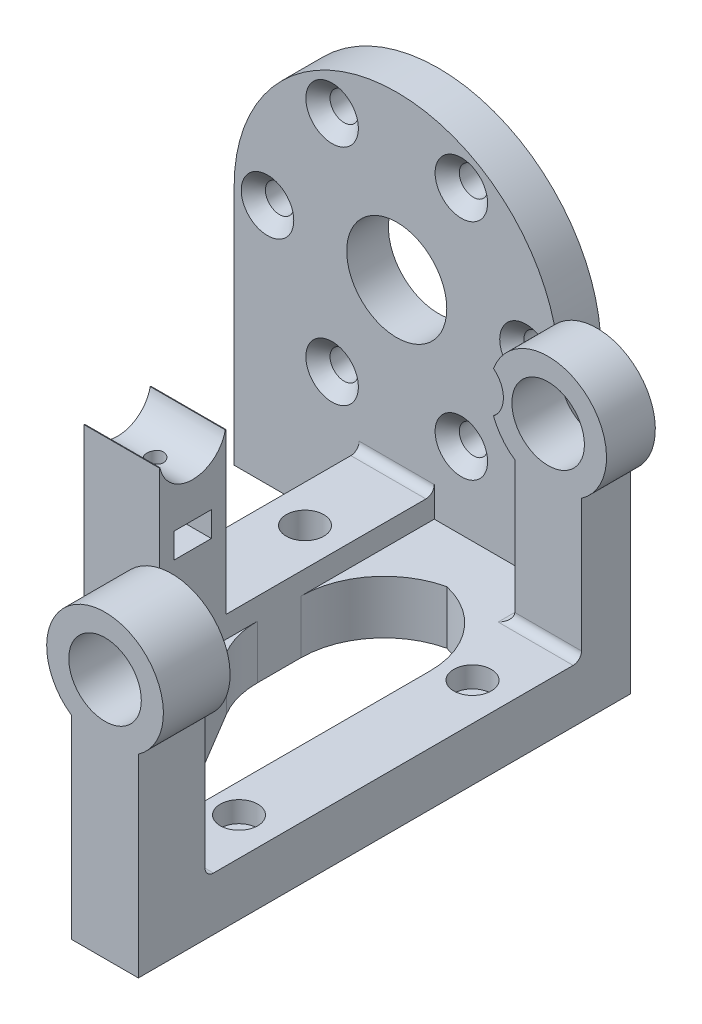
SolidWorks part; units mm, degrees
ref_plane "Front Plane" through (0, 0, 0) normal (0, 0, 1) x (1, 0, 0)
ref_plane "Top Plane" through (0, 0, 0) normal (0, 1, 0) x (1, 0, 0)
ref_plane "Right Plane" through (0, 0, 0) normal (1, 0, 0) x (0, 0, -1)
sketch "Sketch5" plane through (0, 0, 0) normal (0, 0, 1) x (1, 0, 0)
  line L0 (0, 0) -> (0, 15.5) construction
  circle A0 centre (0, 0) radius 19.5
  circle A1 centre (-7.75, 13.4234) radius 1.5
  circle A2 centre (0, 0) radius 6
  circle A3 centre (7.75, 13.4234) radius 1.5
  circle A4 centre (15.5, 0) radius 1.5
  circle A5 centre (7.75, -13.4234) radius 1.5
  circle A6 centre (-7.75, -13.4234) radius 1.5
  circle A7 centre (-15.5, 0) radius 1.5
  point P18 (0, 0)
  dimension "D2" = 3
  dimension "D3" = 39
  dimension "D4" = 12
  dimension "D1" = 15.5
  dimension "D5" = 6
extrude "Boss-Extrude1" add sketch "Sketch5" along normal blind 5
hole_wizard "CSK for M3 Flat Head Machine Screw1" positions "Sketch7" profile "Sketch6" countersink size "M3" standard "ANSI Metric" end condition through all
sketch "Sketch7" plane through (0, 0, 5) normal (0, 0, 1) x (1, 0, 0)
  point P0 (-15.5, 0)
  point P3 (-7.75, 13.4234)
  point P6 (7.75, 13.4234)
  point P9 (15.5, 0)
  point P12 (7.75, -13.4234)
  point P15 (-7.75, -13.4234)
sketch "Sketch6" plane through (-15.5, 0, 5) normal (1, 0, 0) x (0, -1, 0)
  line L0 (0, 0) -> (0, 5)
  line L1 (0, 5) -> (1.7, 5)
  line L2 (1.7, 5) -> (1.7, 1.45)
  line L3 (1.7, 1.45) -> (3.15, 0)
  line L5 (3.15, 0) -> (0, 0)
  line L6 (-1.7, 1.45) -> (-3.15, 0) construction
  line L11 (0, -6.35) -> (0, 107.95) construction
  dimension "Thru Hole Dia." = 3.4
  dimension "Thru Hole Depth" = 5
  dimension "Near C'Sink Dia." = 6.3
  dimension "Near C'Sink Angle" = 90
sketch "Sketch8" plane through (0, 0, 5) normal (0, 0, 1) x (1, 0, 0)
  line L0 (-19.5, 0) -> (-19.5, -25)
  line L1 (-19.5, -25) -> (19.5, -25)
  line L2 (19.5, -25) -> (19.5, 0)
  circle A0 centre (0, 0) radius 19.5 construction
  arc A1 (-19.5, 0) -> (19.5, 0) centre (0, 0) ccw
  dimension "D1" = 25
extrude "Boss-Extrude2" add sketch "Sketch8" against normal up to surface (5 mm away) up to face at (-13.8, 0, 0)
sketch "Sketch9" plane through (0, 0, 5) normal (0, 0, 1) x (1, 0, 0)
  line L0 (-19.5, -25) -> (19.5, -25) construction
  line L4 (-4.5, -20) -> (-4.5, -25)
  line L5 (4.5, -20) -> (-4.5, -25) construction
  line L6 (4.5, -25) -> (-4.5, -20) construction
  line L7 (-19.5, -25) -> (0, -22.5) construction
  line L8 (0, -22.5) -> (19.5, -25) construction
  line L9 (-4.5, -25) -> (4.5, -25)
  line L10 (-4.5, -20) -> (4.5, -20)
  line L11 (4.5, -20) -> (4.5, -25)
  point P0 (0, -22.5)
  dimension "D1" = 5
  dimension "D2" = 9
extrude "Boss-Extrude3" add sketch "Sketch9" along normal blind 32.9817
sketch "Sketch10" plane through (0.3712, -20, 0) normal (0, 1, 0) x (1, 0, 0)
  line L1 (-4.8712, -37.9817) -> (4.1288, -37.9817)
  line L2 (-4.8712, -37.9817) -> (-4.8712, -29.9817)
  line L3 (-4.8712, -29.9817) -> (4.1288, -29.9817)
  line L4 (4.1288, -37.9817) -> (4.1288, -29.9817)
  line L6 (-4.8712, -37.9817) -> (-4.8712, -5) construction
  line L7 (4.1288, -37.9817) -> (4.1288, -5) construction
  dimension "D1" = 8
extrude "Boss-Extrude4" add sketch "Sketch10" along normal blind 24
sketch "Sketch11" plane through (-4.5, 0, 0) normal (-1, 0, 0) x (0, 0, 1)
  line L0 (29.9817, 4) -> (29.9817, -20) construction
  line L2 (29.9817, 4) -> (37.9817, 4) construction
  line L3 (37.9817, 4) -> (37.9817, -25) construction
  line L4 (29.9817, 0) -> (27.1369, 2.0822)
  line L5 (27.1369, 2.0822) -> (27.3574, 4.8482)
  line L6 (27.3574, 4.8482) -> (32.7492, 5.4696)
  line L7 (32.7492, 5.4696) -> (41.4483, 5.0286)
  line L8 (41.4483, 5.0286) -> (40.8237, 2.383)
  line L9 (40.8237, 2.383) -> (37.9817, 0)
  line L10 (29.9817, -0.8) -> (30.0625, -0.8)
  line L11 (37.9009, -0.8) -> (37.9817, -0.8)
  line L12 (37.9817, 0) -> (37.9817, -0.8)
  line L13 (29.9817, -0.8) -> (29.9817, 0)
  arc A0 (30.0625, -0.8) -> (37.9009, -0.8) centre (33.9817, 0) ccw
  dimension "D1" = 0.8
extrude "Cut-Extrude1" cut sketch "Sketch11" against normal blind 20
sketch "Sketch12" plane through (0, -0.8, 0) normal (0, 1, 0) x (1, 0, 0)
  line L0 (-4.5, -29.9817) -> (4.5, -37.9817) construction
  line L1 (4.5, -29.9817) -> (-4.5, -37.9817) construction
  line L2 (4.5, -37.9009) -> (4.5, -30.0625) construction
  line L3 (4.5, -29.9817) -> (4.5, -5) construction
  circle A0 centre (0, -33.9817) radius 1
  dimension "D1" = 2
extrude "Cut-Extrude2" cut sketch "Sketch12" against normal blind 16
sketch "Sketch13" plane through (-4.5, 0, 0) normal (-1, 0, 0) x (0, 0, 1)
  line L0 (29.9817, -8.9707) -> (31.7317, -8.9707) construction
  line L1 (31.7317, -8.2443) -> (36.2317, -8.2443)
  line L2 (31.7317, -8.2443) -> (31.7317, -11.2443)
  line L3 (31.7317, -11.2443) -> (36.2317, -11.2443)
  line L4 (36.2317, -8.2443) -> (36.2317, -11.2443)
  line L5 (29.9817, -0.8) -> (29.9817, -20) construction
  line L6 (37.9817, -0.8) -> (37.9817, -25) construction
  line L7 (36.2317, -8.9707) -> (37.9817, -8.9707) construction
  dimension "D1" = 4.5
  dimension "D2" = 3
extrude "Cut-Extrude3" cut sketch "Sketch13" against normal up to surface (9 mm away)
sketch "Sketch14" plane through (0, -25, 0) normal (0, -1, 0) x (1, 0, 0)
  line L0 (4.5, 37.9817) -> (4.5, 5) construction
  line L1 (4.5, 5) -> (28.015, 5)
  line L2 (4.5, 5) -> (4.5, 11)
  line L3 (4.5, 11) -> (20.015, 11)
  line L4 (28.015, 5) -> (28.015, 12.4921)
  line L5 (28.015, -7.8644) -> (28.015, 29.6173) construction
  line L6 (20.015, 89.1356) -> (20.015, 42.6173) construction
  line L8 (28.015, 12.4921) -> (28.015, 64)
  line L9 (28.015, 64) -> (20.015, 64)
  line L10 (20.015, 11) -> (20.015, 64)
  line L12 (4.5, 5) -> (19.5, 5) construction
  dimension "D1" = 0
  dimension "D2" = 6
  dimension "D3" = 59
extrude "Boss-Extrude5" add sketch "Sketch14" against normal blind 2.4
sketch "Sketch15" plane through (28.015, 0, 0) normal (1, 0, 0) x (0, 0, -1)
  line L0 (-43.6173, 4) -> (-89.1356, 4) construction
  line L1 (-64, -22.6) -> (-56, -22.6)
  line L2 (-64, -22.6) -> (-64, 4)
  line L3 (-64, 4) -> (-56, 4)
  line L4 (-56, -22.6) -> (-56, 4)
  line L6 (-5, -22.6) -> (-13, -22.6)
  line L7 (-5, -22.6) -> (-5, 4)
  line L8 (-5, 4) -> (-13, 4)
  line L9 (-13, -22.6) -> (-13, 4)
  dimension "D1" = 8
extrude "Boss-Extrude6" add sketch "Sketch15" against normal up to surface (8 mm away) up to face at (20.015, -23.8, 37.5)
sketch "Sketch16" plane through (0, 0, 64) normal (0, 0, 1) x (1, 0, 0)
  line L0 (20.015, -1.0579) -> (20.1574, -1.0579)
  line L1 (20.015, 4) -> (20.015, -25) construction
  line L2 (28.015, 4) -> (28.015, -25) construction
  line L3 (28.015, -1.0579) -> (30.9797, 0.9089)
  line L4 (30.9797, 0.9089) -> (30.0419, 7.8056)
  line L5 (20.015, -1.0579) -> (20.015, 9.2476)
  line L6 (20.015, 3) -> (20.015, 15.4952) construction
  line L7 (20.015, 9.2476) -> (30.0419, 7.8056)
  line L8 (27.8726, -1.0579) -> (28.015, -1.0579)
  arc A0 (20.1574, -1.0579) -> (27.8726, -1.0579) centre (24.015, 0) ccw
extrude "Cut-Extrude4" cut sketch "Sketch16" against normal up to surface (59 mm away) up to face at (22.51, -14.5333, 5)
sketch "Sketch17" plane through (0, -22.6, 0) normal (0, 1, 0) x (1, 0, 0)
  line L0 (20.015, -56) -> (20.015, -13) construction
  line L1 (20.015, -13.8581) -> (28.015, -13.8581)
  line L2 (20.015, -13.8581) -> (20.015, -10.8581)
  line L3 (20.015, -10.8581) -> (28.015, -10.8581)
  line L4 (28.015, -13.8581) -> (28.015, -10.8581)
  line L5 (28.015, -5) -> (28.015, -13) construction
  dimension "D1" = 3
extrude "Cut-Extrude5" cut sketch "Sketch17" along normal up to surface (21.5421 mm away) up to face at (20.0862, -1.0579, 9)
sketch "Sketch19" plane through (0, 0, 29.9817) normal (0, 0, -1) x (-1, 0, 0)
  circle A0 centre (-7.75, -13.4234) radius 3
  dimension "D1" = 6
extrude "Cut-Extrude6" [suppressed] cut sketch "Sketch19" against normal through all
sketch "Sketch20" plane through (0, -22.6, 0) normal (0, 1, 0) x (1, 0, 0)
  line L0 (20.015, -64) -> (4.5, -37.9817)
  line L1 (20.015, -55) -> (4.5, -28.9817)
  line L2 (20.015, -56) -> (20.015, -11) construction
  line L3 (4.5, -29.9817) -> (4.5, -5) construction
  line L4 (4.5, -28.9817) -> (4.5, -37.9817)
  line L5 (20.015, -55) -> (20.015, -64)
  dimension "D1" = 9
extrude "Boss-Extrude7" add sketch "Sketch20" against normal up to surface (2.4 mm away) up to face at (8.005, -25, 20.4969)
fillet "Fillet1" radius 10 5 edges at (12.2575, -22.6, 11) (4.5, -23.8, 11) (20.015, -23.8, 11) (12.2575, -25, 11) (4.5, -23.8, 28.9817)
fillet "Fillet2" radius 1 1 edges at (20.015, -23.8, 55)
fillet "Fillet3" radius 1 5 edges at (24.015, -22.6, 56) (20.015, -22.6, 7.9291) (24.015, -22.6, 10.8581) (20.015, -22.6, 60) (0, -20, 5)
sketch "Sketch22" plane through (28.015, 0, 0) normal (1, 0, 0) x (0, 0, -1)
  circle A0 centre (-60, -7.7015) radius 1
extrude "Cut-Extrude7" [suppressed] cut sketch "Sketch22" against normal up to surface (8 mm away)
sketch "Sketch23" plane through (28.015, 0, 0) normal (1, 0, 0) x (0, 0, -1)
  circle A0 centre (-7.9291, -7.7015) radius 1
extrude "Cut-Extrude8" [suppressed] cut sketch "Sketch23" against normal up to surface (8 mm away)
sketch "Sketch24" plane through (0, 0, 5) normal (0, 0, -1) x (-1, 0, 0)
  line L0 (-20.015, -21.6) -> (-20.015, -1.0579) construction
  line L1 (-28.015, -1.0579) -> (-28.015, -25) construction
  line L4 (-20.015, -5.7446) -> (-20.015, -1.0579)
  line L5 (-28.015, -1.0579) -> (-28.015, -5.7446)
  line L6 (-27.8726, -1.0579) -> (-28.015, -1.0579)
  line L7 (-20.015, -1.0579) -> (-20.1574, -1.0579)
  arc A0 (-20.1574, -1.0579) -> (-27.8726, -1.0579) centre (-24.015, 0) ccw
  arc A1 (-20.015, -5.7446) -> (-17.4629, -2.4637) centre (-24.015, 0) ccw
  circle A2 centre (-15.5, 0) radius 3.15 construction
  arc A3 (-17.4629, 2.4637) -> (-17.4629, -2.4637) centre (-15.5, 0) ccw
  arc A4 (-17.4629, 2.4637) -> (-28.015, -5.7446) centre (-24.015, 0) ccw
  dimension "D1" = 14
extrude "Boss-Extrude8" add sketch "Sketch24" against normal up to surface (5.8581 mm away) up to face at (24.015, -8.3956, 10.8581)
sketch "Sketch25" plane through (0, 0, 64) normal (0, 0, 1) x (1, 0, 0)
  line L0 (20.015, -5.7446) -> (20.015, -1.0579)
  line L1 (20.015, -1.0579) -> (20.1574, -1.0579)
  line L2 (27.8726, -1.0579) -> (28.015, -1.0579)
  line L3 (28.015, -1.0579) -> (28.015, -5.7446)
  circle A0 centre (24.015, 0) radius 4 construction
  arc A2 (27.8726, -1.0579) -> (20.1574, -1.0579) centre (24.015, 0) ccw
  arc A3 (28.015, -5.7446) -> (20.015, -5.7446) centre (24.015, 0) ccw
extrude "Boss-Extrude9" add sketch "Sketch25" against normal up to surface (8 mm away) up to face at (24.015, -8.3956, 56)
sketch "Sketch26" plane through (0, 0, 64) normal (0, 0, 1) x (1, 0, 0)
  circle A0 centre (24.015, 0) radius 4.35
  dimension "D1" = 8.7
extrude "Cut-Extrude9" cut sketch "Sketch26" against normal up to surface (59 mm away) up to face at (22.1195, -11.2362, 5)
sketch "Sketch27" plane through (0, -25, 0) normal (0, -1, 0) x (1, 0, 0)
  line L0 (4.5, 26.2265) -> (4.5, 21) construction
  line L1 (20.015, 51.3705) -> (20.015, 21) construction
  line L2 (18.1561, 51.8827) -> (5.9111, 31.3481) construction
  line L3 (4.5, 26.2265) -> (4.5, 21)
  line L4 (20.015, 51.3705) -> (20.015, 21)
  line L5 (18.1561, 51.8827) -> (5.9111, 31.3481)
  line L10 (19.5, 0) -> (19.5, 5)
  line L11 (19.5, 5) -> (28.015, 5)
  line L12 (28.015, 5) -> (28.015, 64)
  line L13 (28.015, 64) -> (20.015, 64)
  line L14 (20.015, 64) -> (4.5, 37.9817)
  line L15 (4.5, 37.9817) -> (-4.5, 37.9817)
  line L16 (-4.5, 37.9817) -> (-4.5, 5)
  line L17 (-4.5, 5) -> (-19.5, 5)
  line L18 (-19.5, 5) -> (-19.5, 0)
  line L19 (-19.5, 0) -> (19.5, 0)
  line L20 (19.5, 0) -> (19.5, 5)
  line L21 (19.5, 5) -> (28.015, 5)
  line L22 (28.015, 5) -> (28.015, 64)
  line L23 (28.015, 64) -> (20.015, 64)
  line L24 (20.015, 64) -> (4.5, 37.9817)
  line L25 (4.5, 37.9817) -> (-4.5, 37.9817)
  line L26 (-4.5, 37.9817) -> (-4.5, 5)
  line L27 (-4.5, 5) -> (-19.5, 5)
  line L28 (-19.5, 5) -> (-19.5, 0)
  line L29 (-19.5, 0) -> (19.5, 0)
  arc A0 (12.2575, 11.2547) -> (20.015, 21) centre (10.015, 21) ccw construction
  arc A1 (4.5, 21) -> (12.2575, 11.2547) centre (14.5, 21) ccw construction
  arc A2 (5.9111, 31.3481) -> (4.5, 26.2265) centre (14.5, 26.2265) ccw construction
  arc A3 (20.015, 51.3705) -> (18.1561, 51.8827) centre (19.015, 51.3705) ccw construction
  arc A4 (12.2575, 11.2547) -> (20.015, 21) centre (10.015, 21) ccw
  arc A5 (4.5, 21) -> (12.2575, 11.2547) centre (14.5, 21) ccw
  arc A6 (5.9111, 31.3481) -> (4.5, 26.2265) centre (14.5, 26.2265) ccw
  arc A7 (20.015, 51.3705) -> (18.1561, 51.8827) centre (19.015, 51.3705) ccw
  dimension "D1" = 0
extrude "Boss-Extrude10" add sketch "Sketch27" along normal blind 4
sketch "Sketch28" plane through (0, -22.6, 0) normal (0, 1, 0) x (1, 0, 0)
  line L0 (23.515, -11.8581) -> (23.515, -55) construction
  line L1 (28.015, -11.8581) -> (19.015, -11.8581) construction
  line L2 (19.015, -55) -> (28.015, -55) construction
  line L3 (23.515, -19.4291) -> (23.515, -33.4291) construction
  line L4 (23.515, -33.4291) -> (23.515, -47.4291) construction
  circle A0 centre (23.515, -19.4291) radius 1
  circle A1 centre (23.515, -47.4291) radius 1
  dimension "D1" = 2
  dimension "D2" = 28
  dimension "D3" = 14
extrude "Cut-Extrude10" cut sketch "Sketch28" against normal through all
sketch "Sketch29" plane through (0, -22.6, 0) normal (0, 1, 0) x (1, 0, 0)
  circle A0 centre (23.515, -19.4291) radius 2.25
  circle A1 centre (23.515, -47.4291) radius 2.25
  dimension "D1" = 4.5
extrude "Cut-Extrude11" cut sketch "Sketch29" against normal blind 2.5
sketch "Sketch30" plane through (0, -20, 0) normal (0, 1, 0) x (1, 0, 0)
  line L0 (4.5, -6) -> (-4.5, -6) construction
  circle A0 centre (0, -16) radius 1
  dimension "D1" = 2
  dimension "D2" = 10
extrude "Cut-Extrude12" cut sketch "Sketch30" against normal through all
sketch "Sketch31" plane through (0, -20, 0) normal (0, 1, 0) x (1, 0, 0)
  circle A0 centre (0, -16) radius 2.25
  dimension "D1" = 4.5
extrude "Cut-Extrude13" cut sketch "Sketch31" against normal blind 5
